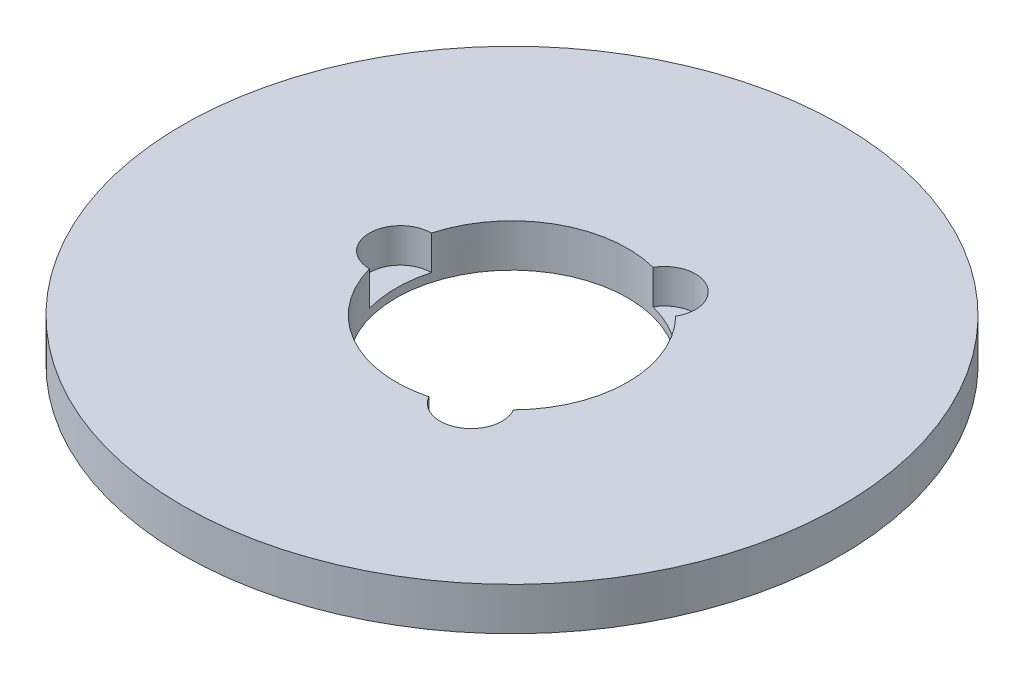
SolidWorks part; units mm, degrees
ref_plane "Front Plane" through (0, 0, 0) normal (0, 0, 1) x (1, 0, 0)
ref_plane "Top Plane" through (0, 0, 0) normal (0, 1, 0) x (1, 0, 0)
ref_plane "Right Plane" through (0, 0, 0) normal (1, 0, 0) x (0, 0, -1)
sketch "Sketch1" plane through (0, 0, 0) normal (0, 1, 0) x (1, 0, 0)
  circle A0 centre (0, 0) radius 92.5
  dimension "FLANGE_OD" = 185
extrude "Boss-Extrude1" add sketch "Sketch1" along normal blind 12
sketch "Sketch2" plane through (0, 0, 0) normal (0, 1, 0) x (1, 0, 0)
  circle A0 centre (0, 0) radius 32.5
  dimension "BORE_D" = 65
extrude "Cut-Extrude1" cut sketch "Sketch2" along normal through all
sketch "Sketch3" plane through (0, 12, 0) normal (0, 1, 0) x (1, 0, 0)
  circle A0 centre (0, 0) radius 31.3222 construction
  circle A1 centre (-31.3222, 0) radius 8.6928
  dimension "BOLT_D" = 17.3855
  dimension "BOLT_PCD" = 62.6444
extrude "Cut-Extrude2" cut sketch "Sketch3" against normal blind 9.6103
pattern_circular "CirPattern1" count 3 over 360 about axis through (0, 0, 0) along (0, 1, 0) of "Cut-Extrude2"
